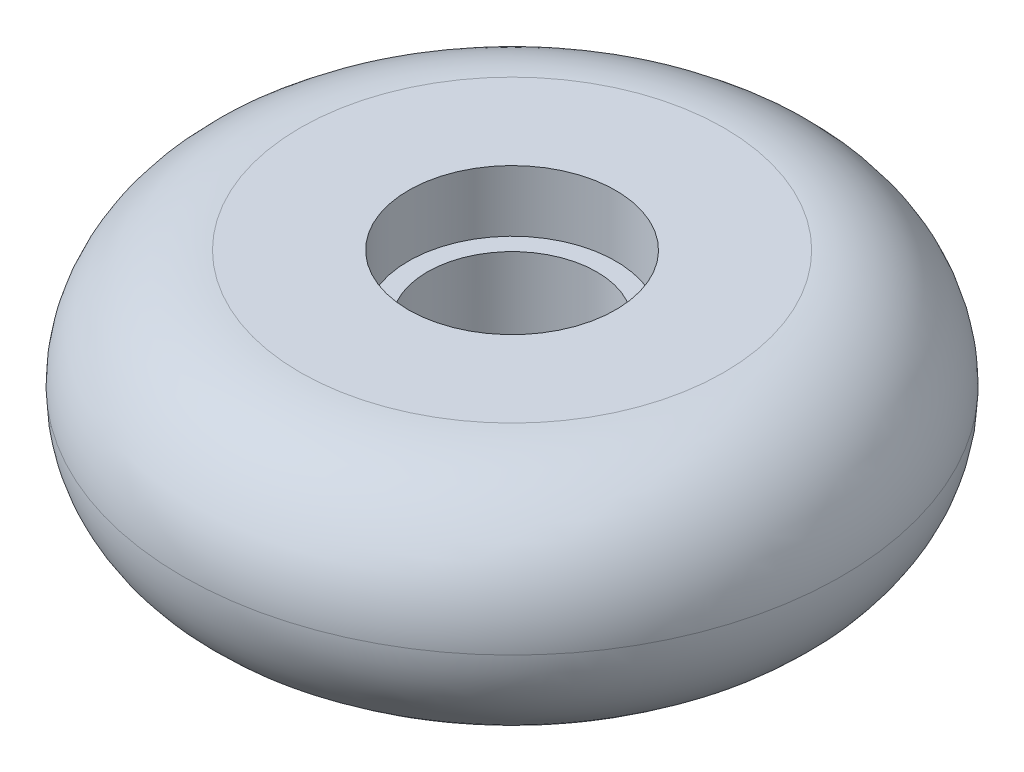
SolidWorks part; units mm, degrees
ref_plane "Front Plane" through (0, 0, 0) normal (0, 0, 1) x (1, 0, 0)
ref_plane "Top Plane" through (0, 0, 0) normal (0, 1, 0) x (1, 0, 0)
ref_plane "Right Plane" through (0, 0, 0) normal (1, 0, 0) x (0, 0, -1)
sketch "Sketch1" plane through (0, 0, 0) normal (0, 1, 0) x (1, 0, 0)
  circle A0 centre (0, 0) radius 35
  dimension "D1" = 70
extrude "Boss-Extrude1" add sketch "Sketch1" along normal blind 25
fillet "Fillet1" radius 12.5 2 edges at (0, 0, 35) (0, 25, 35)
sketch "Sketch2" plane through (0, 25, 0) normal (0, 1, 0) x (1, 0, 0)
  circle A0 centre (0, 0) radius 11
  dimension "D1" = 22
extrude "Cut-Extrude1" cut sketch "Sketch2" against normal blind 6.5
sketch "Sketch3" plane through (0, 0, 0) normal (0, -1, 0) x (1, 0, 0)
  circle A0 centre (0, 0) radius 11
  dimension "D1" = 22
extrude "Cut-Extrude2" cut sketch "Sketch3" against normal blind 6.5
sketch "Sketch4" plane through (0, 6.5, 0) normal (0, -1, 0) x (1, 0, 0)
  circle A0 centre (0, 0) radius 9
  dimension "D1" = 18
extrude "Cut-Extrude3" cut sketch "Sketch4" against normal through all
